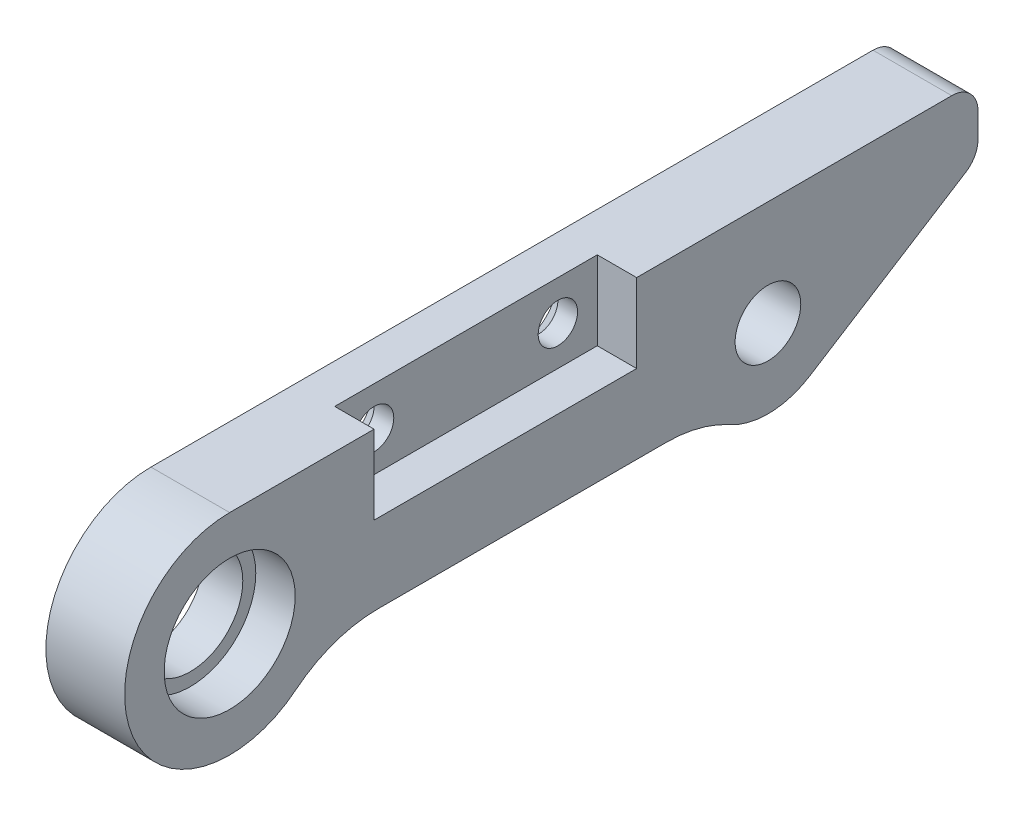
SolidWorks part; units mm, degrees
material "1060 Alloy"
ref_plane "Front Plane" through (0, 0, 0) normal (0, 0, 1) x (1, 0, 0)
ref_plane "Top Plane" through (0, 0, 0) normal (0, 1, 0) x (1, 0, 0)
ref_plane "Right Plane" through (0, 0, 0) normal (1, 0, 0) x (0, 0, -1)
sketch "Sketch27" plane through (0, 0, 0) normal (1, 0, 0) x (0, 0, -1)
  line L2 (9, 50) -> (66, 50)
  line L3 (9, 42) -> (30.9317, 42) construction
  line L4 (30.9317, 42) -> (30.9317, 54) construction
  line L6 (9, 34) -> (48.5644, 34)
  line L7 (30.9317, 54) -> (9, 42) construction
  line L8 (0, 0) -> (60, 0) construction
  line L9 (0, 0) -> (0, 58) construction
  line L10 (0, 58) -> (60, 58) construction
  line L11 (60, 0) -> (60, 58) construction
  line L12 (66, 50) -> (66, 45)
  line L13 (48.5644, 34) -> (66, 45)
  arc A0 (9, 50) -> (9, 34) centre (9, 42) ccw
  circle A1 centre (50, 42) radius 6 construction
  circle A3 centre (9, 42) radius 5.6 construction
  circle A5 centre (9, 42) radius 4
  circle A6 centre (50, 42) radius 2.5
  dimension "D9" = 12
  dimension "D10" = 5
  dimension "D12" = 8
  dimension "D13" = 8
  dimension "D14" = 5
  dimension "D6" = 16
  dimension "D16" = 11.2
  dimension "D1" = 60
  dimension "D2" = 58
  dimension "D3" = 42
  dimension "D4" = 9
  dimension "D5" = 50
  dimension "D7" = 42
  dimension "D8" = 12
  dimension "D17" = 25
extrude "Boss-Extrude1" add sketch "Sketch27" along normal blind 6
sketch "Sketch33" plane through (6, 0, 0) normal (1, 0, 0) x (0, 0, -1)
  circle A0 centre (9, 42) radius 4.99
  dimension "D1" = 9.98
extrude "Cut-Extrude2" cut sketch "Sketch33" against normal blind 3
sketch "Sketch34" plane through (6, 0, 0) normal (1, 0, 0) x (0, 0, -1)
  line L0 (20, 44) -> (40, 44)
  line L1 (20, 44) -> (20, 50)
  line L2 (40, 44) -> (40, 50)
  line L3 (20, 50) -> (40, 50)
  line L5 (9, 42) -> (43.3727, 42) construction
  circle A0 centre (50, 42) radius 2.5 construction
  dimension "D1" = 20
  dimension "D2" = 6
  dimension "D3" = 10
  dimension "D4" = 2
extrude "Cut-Extrude3" cut sketch "Sketch34" against normal blind 3
sketch "Sketch36" plane through (3, 0, 0) normal (1, 0, 0) x (0, 0, -1)
  line L0 (20, 50) -> (20, 44) construction
  line L2 (40, 44) -> (40, 50) construction
  line L3 (20, 44) -> (40, 44) construction
  circle A0 centre (23, 47) radius 1.5
  circle A1 centre (37, 47) radius 1.5
  dimension "D1" = 3
  dimension "D2" = 3
  dimension "D3" = 3
  dimension "D5" = 3
extrude "Cut-Extrude5" cut sketch "Sketch36" against normal up to next
fillet "Fillet3" radius 2 2 edges at (3, 50, -66) (3, 45, -66)
fillet "Fillet4" radius 10 1 edges at (3, 34, -48.5644)
sketch "Sketch37" plane through (6, 0, 0) normal (1, 0, 0) x (0, 0, -1)
  line L1 (9, 34) -> (45.6736, 34) construction
  line L2 (20.3137, 38) -> (42.254, 38)
  line L3 (51.0093, 35.5425) -> (65.0672, 44.4115) construction
  line L4 (9, 34) -> (53.2015, 34)
  line L5 (53.2015, 34) -> (53.2015, 36.9255)
  line L6 (20, 44) -> (40, 44) construction
  arc A0 (9, 34) -> (14.0283, 35.7778) centre (9, 42) ccw
  arc A1 (14.0283, 35.7778) -> (20.3137, 38) centre (20.3137, 28) cw
  arc A2 (42.254, 38) -> (47.0953, 36.75) centre (42.254, 28) cw
  arc A3 (47.0953, 36.75) -> (53.2015, 36.9255) centre (50, 42) ccw
  circle A4 centre (50, 42) radius 2.5 construction
  circle A5 centre (9, 42) radius 4.99 construction
  dimension "D2" = 10
  dimension "D1" = 6
extrude "Cut-Extrude6" cut sketch "Sketch37" against normal up to next
chamfer "Chamfer1" distance 1.5 angle 45 2 edges at (0, 47, -24.5) (0, 47, -38.5)
